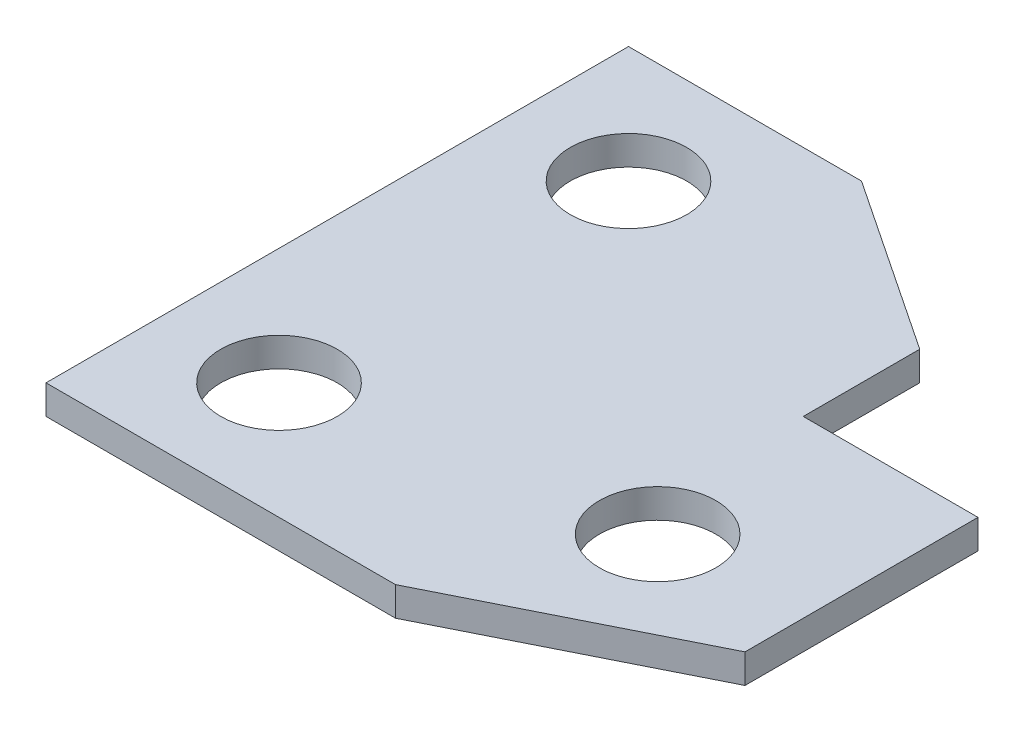
SolidWorks part; units mm, degrees
ref_plane "Front Plane" through (0, 0, 0) normal (0, 0, 1) x (1, 0, 0)
ref_plane "Top Plane" through (0, 0, 0) normal (0, 1, 0) x (1, 0, 0)
ref_plane "Right Plane" through (0, 0, 0) normal (1, 0, 0) x (0, 0, -1)
sketch "Sketch1" plane through (0, 0, 0) normal (0, 1, 0) x (1, 0, 0)
  line L0 (-27.1641, 31.1406) -> (-27.1641, -68.8594)
  line L1 (-27.1641, -68.8594) -> (32.8359, -68.8594)
  line L2 (32.8359, -68.8594) -> (72.8359, -48.8594)
  line L3 (72.8359, -48.8594) -> (72.8359, -8.8594)
  line L4 (72.8359, -8.8594) -> (42.8359, -8.8594)
  line L5 (42.8359, -8.8594) -> (42.8359, 11.1406)
  line L6 (42.8359, 11.1406) -> (12.8359, 31.1406)
  line L7 (12.8359, 31.1406) -> (-27.1641, 31.1406)
  circle A0 centre (-7.1641, 11.1406) radius 10
  circle A1 centre (-7.1641, -48.8594) radius 10
  circle A2 centre (47.8359, -38.8594) radius 10
  dimension "D12" = 20
  dimension "D13" = 20
  dimension "D14" = 20
  dimension "D1" = 100
  dimension "D2" = 60
  dimension "D3" = 60
  dimension "D4" = 40
  dimension "D5" = 20
  dimension "D6" = 20
  dimension "D7" = 70
  dimension "D8" = 100
  dimension "D9" = 60
  dimension "D10" = 20
  dimension "D11" = 20
  dimension "D15" = 30
  dimension "D16" = 75
extrude "Boss-Extrude1" add sketch "Sketch1" along normal blind 5 contours L5 L6 L7 L0 L1 L2 L3 L4
extrude "Cut-Extrude6" cut sketch "Sketch1<7>" against normal through all and the other way through all contours A0 | A1 | A2
sketch "Sketch1<7>" plane through (0, 0, 0) normal (0, 1, 0) x (1, 0, 0) same geometry as "Sketch1"
